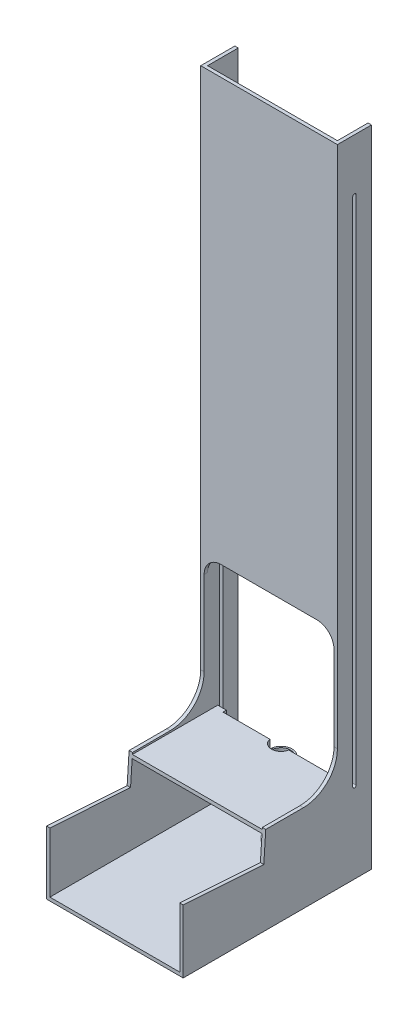
SolidWorks part; units mm, degrees
material "AISI 4340 Steel, annealed"
ref_plane "Front Plane" through (0, 0, 0) normal (0, 0, 1) x (1, 0, 0)
ref_plane "Top Plane" through (0, 0, 0) normal (0, 1, 0) x (1, 0, 0)
ref_plane "Right Plane" through (0, 0, 0) normal (1, 0, 0) x (0, 0, -1)
ref_plane "Right side of elevator platform" through (190.5, 0, 0) normal (1, 0, 0) x (0, 0, -1)
sketch "Sketch2" plane through (190.5, 0, 0) normal (1, 0, 0) x (0, 0, -1)
  line L0 (50, 236.5) -> (50, 1736.5) construction
  line L1 (45, 236.5) -> (45, 1736.5)
  line L2 (55, 236.5) -> (55, 1736.5)
  line L4 (0, 0) -> (100, 0)
  line L5 (0, 0) -> (0, 1800)
  line L6 (0, 1800) -> (100, 1800)
  line L7 (100, 0) -> (100, 1800)
  arc A0 (45, 236.5) -> (55, 236.5) centre (50, 236.5) ccw
  arc A1 (55, 1736.5) -> (45, 1736.5) centre (50, 1736.5) ccw
  point P2 (50, 986.5)
  dimension "D6" = 5
  dimension "D1" = 1800
  dimension "D2" = 100
  dimension "D3" = 50
  dimension "D4" = 236.5
  dimension "D5" = 63.5
extrude "Right side guide" add sketch "Sketch2" along normal blind 10
sketch "Sketch3" plane through (190.5, 0, 0) normal (-1, 0, 0) x (0, 0, 1)
  line L0 (0, 1800) -> (0, 0) construction
  line L1 (-100, 0) -> (0, 0)
  line L2 (-100, 0) -> (-100, 10)
  line L3 (-100, 10) -> (0, 10)
  line L4 (0, 0) -> (0, 10)
  dimension "D1" = 10
extrude "Bottom connection" add sketch "Sketch3" along normal blind 381
sketch "Sketch4" plane through (-190.5, 0, 0) normal (-1, 0, 0) x (0, 0, 1)
  line L0 (-55, 236.5) -> (-55, 1736.5) construction
  line L1 (-45, 1736.5) -> (-45, 236.5) construction
  line L2 (-55, 236.5) -> (-55, 1736.5)
  line L3 (-45, 1736.5) -> (-45, 236.5)
  line L4 (-100, 10) -> (0, 10)
  line L5 (0, 10) -> (0, 1800)
  line L6 (0, 1800) -> (-100, 1800)
  line L7 (-100, 1800) -> (-100, 10)
  line L9 (0, 10) -> (0, 1800)
  line L10 (0, 1800) -> (-100, 1800)
  line L11 (-100, 1800) -> (-100, 10)
  line L16 (-100, 10) -> (-100, 0)
  line L17 (-100, 0) -> (0, 0)
  line L18 (0, 0) -> (0, 10)
  line L19 (0, 10) -> (-100, 10)
  line L20 (-100, 10) -> (-100, 0)
  line L21 (-100, 0) -> (0, 0)
  line L22 (0, 0) -> (0, 10)
  arc A0 (-45, 1736.5) -> (-55, 1736.5) centre (-50, 1736.5) ccw construction
  arc A1 (-55, 236.5) -> (-45, 236.5) centre (-50, 236.5) ccw construction
  arc A2 (-45, 1736.5) -> (-55, 1736.5) centre (-50, 1736.5) ccw
  arc A3 (-55, 236.5) -> (-45, 236.5) centre (-50, 236.5) ccw
  dimension "D1" = 0
  dimension "D2" = 0
extrude "Left side guide" add sketch "Sketch4" along normal blind 10
sketch "Sketch5" plane through (0, 0, 0) normal (0, 0, 1) x (1, 0, 0)
  line L0 (-190.5, 10) -> (-190.5, 1800) construction
  line L1 (-190.5, 1800) -> (190.5, 1800)
  line L2 (-190.5, 1800) -> (-190.5, 653.8)
  line L3 (-190.5, 653.8) -> (190.5, 653.8)
  line L4 (190.5, 1800) -> (190.5, 653.8)
  line L5 (190.5, 1800) -> (190.5, 10) construction
  line L6 (200.5, 1800) -> (190.5, 1800) construction
  line L7 (-190.5, 10) -> (190.5, 10) construction
  dimension "D1" = 643.8
extrude "Structural webbing extrude" add sketch "Sketch5" against normal blind 10
sketch "Sketch6" plane through (0, 0, 0) normal (0, 0, 1) x (1, 0, 0)
  line L0 (-200.5, 251.5) -> (-200.5, 0)
  line L1 (-200.5, 0) -> (-200.5, 1800) construction
  line L2 (-200.5, 0) -> (200.5, 0)
  line L3 (200.5, 0) -> (200.5, 251.5)
  line L4 (200.5, 1800) -> (200.5, 0) construction
  line L5 (200.5, 251.5) -> (190.5, 251.5)
  line L6 (190.5, 653.8) -> (190.5, 10) construction
  line L7 (190.5, 251.5) -> (190.5, 10)
  line L8 (190.5, 10) -> (-190.5, 10)
  line L9 (-190.5, 10) -> (-190.5, 251.5)
  line L10 (-190.5, 10) -> (-190.5, 653.8) construction
  line L11 (-190.5, 251.5) -> (-200.5, 251.5)
  dimension "D1" = 241.5
extrude "Input roller holder extrude" add sketch "Sketch6" along normal blind 452.52
sketch "Sketch7" plane through (190.5, 0, 0) normal (-1, 0, 0) x (0, 0, 1)
  line L0 (0, 653.8) -> (0, 251.5) construction
  line L1 (452.52, 251.5) -> (-40, 251.5)
  line L2 (452.52, 251.5) -> (452.52, 241.5)
  line L3 (452.52, 241.5) -> (-40, 241.5)
  line L4 (-40, 251.5) -> (-40, 241.5)
  dimension "D1" = 40
  dimension "D2" = 10
extrude "Input roller platform" add sketch "Sketch7" along normal up to next
sketch "Sketch8" plane through (0, 251.5, 0) normal (0, 1, 0) x (1, 0, 0)
  line L1 (-200.5, -452.52) -> (-190.5, -452.52)
  line L2 (-200.5, -452.52) -> (-200.5, 0)
  line L3 (-200.5, 0) -> (-190.5, 0)
  line L4 (-190.5, -452.52) -> (-190.5, 0)
  line L5 (190.5, 0) -> (200.5, 0)
  line L6 (190.5, 0) -> (190.5, -452.52)
  line L7 (190.5, -452.52) -> (200.5, -452.52)
  line L8 (200.5, 0) -> (200.5, -452.52)
extrude "Siding outline" add sketch "Sketch8" along normal blind 5
sketch "Sketch9" plane through (0, 1800, 0) normal (0, 1, 0) x (1, 0, 0)
  line L8 (190.5, 100) -> (190.5, 10)
  line L9 (190.5, 10) -> (-190.5, 10)
  line L10 (-190.5, 10) -> (-190.5, 100)
  line L11 (-190.5, 100) -> (-200.5, 100)
  line L12 (-200.5, 100) -> (-200.5, 0)
  line L13 (-200.5, 0) -> (200.5, 0)
  line L14 (200.5, 0) -> (200.5, 100)
  line L15 (200.5, 100) -> (190.5, 100)
  line L16 (190.5, 100) -> (190.5, 10)
  line L17 (190.5, 10) -> (-190.5, 10)
  line L18 (-190.5, 10) -> (-190.5, 100)
  line L19 (-190.5, 100) -> (-200.5, 100)
  line L20 (-200.5, 100) -> (-200.5, 0)
  line L21 (-200.5, 0) -> (200.5, 0)
  line L22 (200.5, 0) -> (200.5, 100)
  line L23 (200.5, 100) -> (190.5, 100)
  dimension "D1" = 0
extrude "Lip to prevent box from falling out" add sketch "Sketch9" along normal blind 91.5
fillet "Vertical section fillets" radius 100 2 edges at (195.5, 256.5, 0) (-195.5, 256.5, 0)
fillet "Smaller fillets" radius 50 2 edges at (190.5, 653.8, -5) (-190.5, 653.8, -5)
sketch "Sketch11" plane through (0, 0, -40) normal (0, 0, -1) x (-1, 0, 0)
  line L0 (190.5, 251.5) -> (-190.5, 251.5) construction
  line L1 (-165.5, 251.5) -> (165.5, 251.5)
  line L2 (-165.5, 251.5) -> (-165.5, 241.5)
  line L3 (-165.5, 241.5) -> (165.5, 241.5)
  line L4 (165.5, 251.5) -> (165.5, 241.5)
  line L5 (190.5, 241.5) -> (-190.5, 241.5) construction
  line L6 (-190.5, 251.5) -> (-190.5, 241.5) construction
  line L7 (190.5, 251.5) -> (190.5, 241.5) construction
  dimension "D1" = 25
  dimension "D2" = 25
extrude "Gate spacing cut" cut sketch "Sketch11" against normal blind 10
sketch "Sketch12" plane through (-190.5, 0, 0) normal (1, 0, 0) x (0, 0, -1)
  line L1 (45, 221.5) -> (40, 221.5)
  line L2 (45, 221.5) -> (45, 10)
  line L3 (45, 10) -> (40, 10)
  line L4 (40, 221.5) -> (40, 10)
  line L5 (100, 1891.5) -> (100, 10) construction
  line L6 (45, 236.5) -> (45, 1736.5) construction
  line L7 (-452.52, 10) -> (100, 10) construction
  line L8 (40, 241.5) -> (-452.52, 241.5) construction
  line L9 (30, 241.5) -> (25, 241.5)
  line L10 (30, 241.5) -> (30, 10)
  line L11 (30, 10) -> (25, 10)
  line L12 (25, 241.5) -> (25, 10)
  dimension "D1" = 60
  dimension "D2" = 20
  dimension "D3" = 5
extrude "Gate guide rails" add sketch "Sketch12" along normal up to next
sketch "Sketch13" plane through (0, 0, -45) normal (0, 0, -1) x (-1, 0, 0)
  line L0 (-190.5, 221.5) -> (190.5, 221.5) construction
  line L1 (-150.5, 221.5) -> (150.5, 221.5)
  line L2 (-150.5, 221.5) -> (-150.5, 10)
  line L3 (-150.5, 10) -> (150.5, 10)
  line L4 (150.5, 221.5) -> (150.5, 10)
  line L5 (190.5, 10) -> (-190.5, 10) construction
  line L6 (-190.5, 10) -> (-190.5, 1891.5) construction
  point P8 (0, 221.5)
  dimension "D1" = 40
extrude "Gate rod connection cutout" cut sketch "Sketch13" against normal through all
sketch "Sketch14" plane through (0, 10, 0) normal (0, 1, 0) x (1, 0, 0)
  line L0 (150.5, 45) -> (-150.5, 25) construction
  circle A0 centre (0, 35) radius 28
  circle A1 centre (0, 35) radius 33
  point P7 (0, 35)
  dimension "D1" = 56
  dimension "D2" = 5
extrude "Spring cup" add sketch "Sketch14" along normal blind 75
sketch "Sketch15" plane through (0, 85, 0) normal (0, 1, 0) x (1, 0, 0)
  line L0 (190.5, 30) -> (150.5, 30) construction
  line L1 (32.619, 30) -> (27.55, 30)
  line L3 (32.619, 40) -> (27.55, 40)
  line L5 (-27.55, 40) -> (-32.619, 40)
  line L6 (-27.55, 30) -> (-32.619, 30)
  circle A0 centre (0, 35) radius 28 construction
  arc A1 (27.55, 40) -> (-27.55, 40) centre (0, 35) ccw
  circle A2 centre (0, 35) radius 33 construction
  arc A3 (32.619, 40) -> (-32.619, 40) centre (0, 35) ccw
  arc A4 (-27.55, 30) -> (27.55, 30) centre (0, 35) ccw
  arc A5 (-32.619, 30) -> (32.619, 30) centre (0, 35) ccw
extrude "Spring container extension" add sketch "Sketch15" along normal up to surface (136.5 mm away) up to face at (0, 221.5, -27.5)
sketch "Sketch16" plane through (0, 221.5, 0) normal (0, 1, 0) x (1, 0, 0)
  circle A0 centre (0, 35) radius 28
  arc A1 (27.55, 40) -> (-27.55, 40) centre (0, 35) ccw construction
extrude "Spring hole (can't insert spring without this)" cut sketch "Sketch16" along normal up to surface (30 mm away) up to face at (0, 251.5, 85.63)
sketch "Sketch17" plane through (0, 221.5, 0) normal (0, 1, 0) x (1, 0, 0)
  line L2 (-26.1534, 25) -> (-31.4484, 25)
  line L3 (31.4484, 25) -> (26.1534, 25)
  line L4 (-26.1534, 25) -> (-31.4484, 25)
  line L5 (31.4484, 25) -> (26.1534, 25)
  arc A2 (-31.4484, 25) -> (31.4484, 25) centre (0, 35) ccw
  arc A3 (-26.1534, 25) -> (26.1534, 25) centre (0, 35) ccw
  arc A4 (-31.4484, 25) -> (31.4484, 25) centre (0, 35) ccw
  arc A5 (-26.1534, 25) -> (26.1534, 25) centre (0, 35) ccw
  dimension "D1" = 0
extrude "Container extension to meet with conveyor plate" add sketch "Sketch17" along normal up to next
fillet "Spring holder fillets" radius 10 4 edges at (0, 10, -68) (-31.4484, 231.5, -25) (31.4484, 231.5, -25) (0, 241.5, -2)
sketch "Sketch18" plane through (200.5, 0, 0) normal (1, 0, 0) x (0, 0, -1)
  line L0 (-452.52, 256.5) -> (-210.2672, 256.5)
  line L1 (-452.52, 256.5) -> (-100, 256.5) construction
  line L2 (-207.0894, 304.825) -> (-215.631, 174.9305) construction
  line L3 (-210.2672, 256.5) -> (-215.9435, 170.1783)
  line L4 (-215.9435, 170.1783) -> (-452.52, 185.7352)
  line L5 (-452.52, 0) -> (-452.52, 256.5) construction
  line L6 (-452.52, 185.7352) -> (-452.52, 256.5)
  line L7 (-228.6162, 171.0116) -> (-1641.6144, 263.9283) construction
extrude "Cut-Extrude1" cut sketch "Sketch18" against normal through all both and the other way through all
